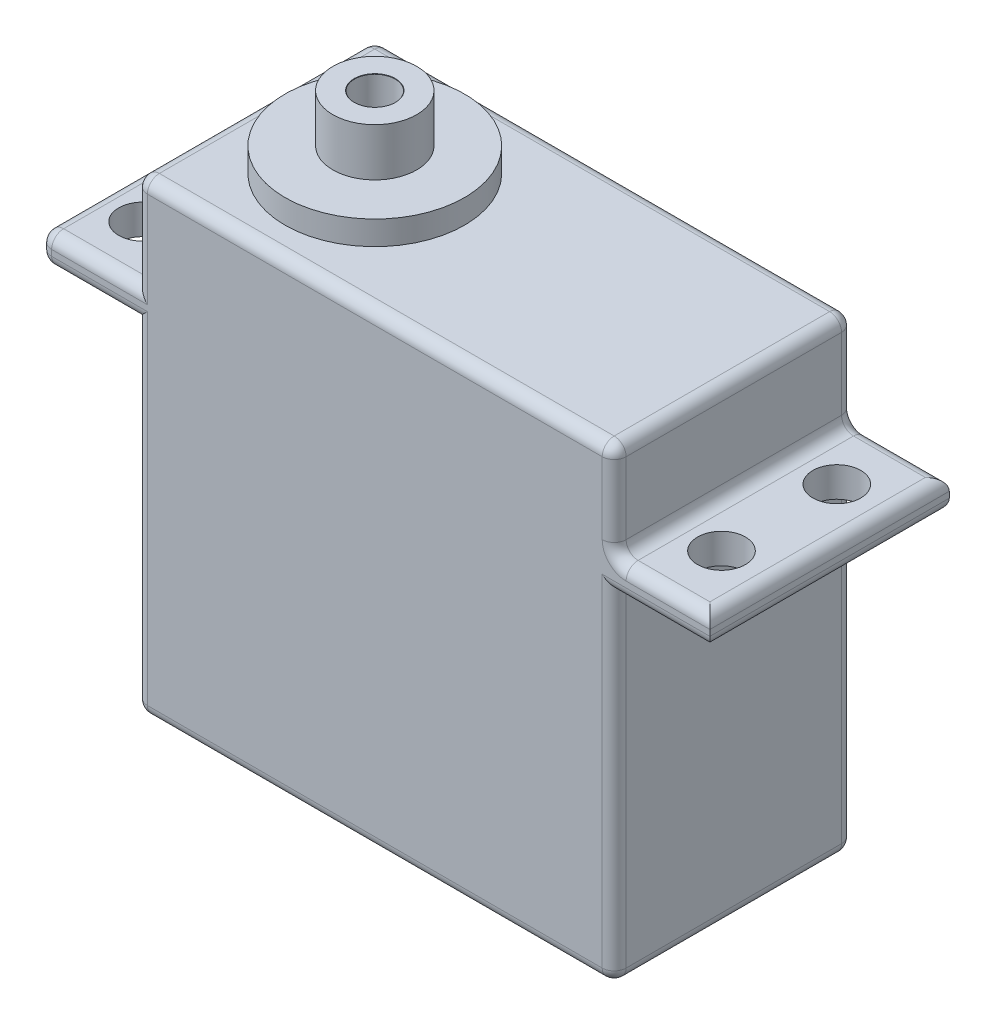
SolidWorks part; units mm, degrees
ref_plane "前视基准面" through (0, 0, 0) normal (0, 0, 1) x (1, 0, 0)
ref_plane "上视基准面" through (0, 0, 0) normal (0, 1, 0) x (1, 0, 0)
ref_plane "右视基准面" through (0, 0, 0) normal (1, 0, 0) x (0, 0, -1)
other "Configuration Table"
sketch "草图1" plane through (0, 0, 0) normal (0, 0, 1) x (1, 0, 0)
  line L1 (-20, -19.5) -> (20, -19.5)
  line L2 (-20, -19.5) -> (-20, 19.5)
  line L3 (-20, 19.5) -> (20, 19.5)
  line L4 (20, -19.5) -> (20, 19.5)
  line L5 (-20, -19.5) -> (20, 19.5) construction
  line L6 (-20, 19.5) -> (20, -19.5) construction
  point P0 (0, 0)
  dimension "D1" = 40
  dimension "D2" = 39
extrude "凸台-拉伸1" add sketch "草图1" against normal blind 20
ref_plane "基准面1" through (20, 0, 0) normal (1, 0, 0) x (0, 0, -1)
ref_plane "基准面2" through (-20, 0, 0) normal (-1, 0, 0) x (0, 0, 1)
sketch "草图2" plane through (20, 0, 0) normal (1, 0, 0) x (0, 0, -1)
  line L0 (0, -19.5) -> (0, 19.5) construction
  line L1 (0, 11.5) -> (20, 11.5)
  line L2 (0, 11.5) -> (0, 9)
  line L3 (0, 9) -> (20, 9)
  line L4 (20, 11.5) -> (20, 9)
  line L5 (20, -19.5) -> (20, 19.5) construction
  line L6 (20, -19.5) -> (0, -19.5) construction
  dimension "D1" = 31
  dimension "D2" = 2.5
extrude "凸台-拉伸2" add sketch "草图2" along normal blind 8
sketch "草图3" plane through (-20, 0, 0) normal (-1, 0, 0) x (0, 0, 1)
  line L0 (-20, 19.5) -> (-20, -19.5) construction
  line L1 (-20, 11.5) -> (0, 11.5)
  line L2 (-20, 11.5) -> (-20, 9)
  line L3 (-20, 9) -> (0, 9)
  line L4 (0, 11.5) -> (0, 9)
  line L5 (0, 19.5) -> (0, -19.5) construction
  line L6 (-20, -19.5) -> (0, -19.5) construction
  dimension "D1" = 31
  dimension "D2" = 2.5
extrude "凸台-拉伸3" add sketch "草图3" along normal blind 8
ref_plane "基准面4" through (0, 11.5, 0) normal (0, 1, 0) x (1, 0, 0)
ref_plane "基准面5" through (0, 11.5, 0) normal (0, 1, 0) x (1, 0, 0)
sketch "草图4" plane through (0, 11.5, 0) normal (0, 1, 0) x (1, 0, 0)
  circle A0 centre (-24.2083, 14.8125) radius 2
  circle A1 centre (-24.2083, 4.8125) radius 2
  circle A2 centre (23.7917, 14.8125) radius 2
  circle A4 centre (23.7917, 5.1765) radius 2
  point P0 (-24.2083, 14.8125)
  point P1 (-24.2083, 4.8125)
  point P2 (23.7917, 14.8125)
  point P3 (23.7917, 5.1765)
  dimension "D3" = 4
  dimension "D4" = 4
  dimension "D5" = 4
  dimension "D6" = 4
  dimension "D1" = 10
  dimension "D2" = 48
extrude "切除-拉伸1" cut sketch "草图4" against normal blind 2.5
ref_plane "基准面7" through (0, 19.5, 0) normal (0, 1, 0) x (1, 0, 0)
sketch "草图6" plane through (0, 19.5, 0) normal (0, 1, 0) x (1, 0, 0)
  line L0 (20, 20) -> (-20, 20) construction
  line L1 (-20, 11) -> (-20, -11) construction
  circle A0 centre (-10, 10) radius 7.5
  dimension "D3" = 15
  dimension "D1" = 10
  dimension "D2" = 10
extrude "凸台-拉伸4" add sketch "草图6" along normal blind 2
sketch "草图8" plane through (0, 19.5, 0) normal (0, 1, 0) x (1, 0, 0)
  line L0 (20, 20) -> (-20, 20) construction
  line L2 (-20, 11) -> (-20, -11) construction
  circle A0 centre (-10, 10) radius 3.5001
  point P6 (-18.3518, -8.0634)
  dimension "D1" = 10
  dimension "D2" = 10
extrude "凸台-拉伸5" add sketch "草图8" along normal blind 6
ref_plane "基准面12" through (0, 25.5, 0) normal (0, 1, 0) x (1, 0, 0)
sketch "草图11" plane through (0, 25.5, 0) normal (0, 1, 0) x (1, 0, 0)
  point P0 (-10, 10)
hole_wizard "M3 间隙孔1" positions "草图12" profile "草图13" hole size "M3" standard "IS"
sketch "草图12" plane through (0, 25.5, 0) normal (0, 1, 0) x (1, 0, 0)
  point P0 (-10, 10)
sketch "草图13" plane through (-10, 25.5, -10) normal (1, 0, 0) x (0, 0, 1)
  line L0 (0, 0) -> (0, 6.0215)
  line L1 (0, 6.0215) -> (1.7, 5)
  line L2 (1.7, 5) -> (1.7, 0.025)
  line L3 (1.7, 0.025) -> (1.725, 0)
  line L5 (1.725, 0) -> (0, 0)
  line L6 (-1.7, 0.025) -> (-1.725, 0) construction
  line L10 (0, 6.0215) -> (-1.7, 5) construction
  line L11 (0, -6.35) -> (0, 107.95) construction
  dimension "孔直径" = 3.4
  dimension "孔深度" = 5
  dimension "近端锥形沉头孔直径" = 3.45
  dimension "近端锥形沉头孔角度" = 90
  dimension "导头角度" = 118
fillet "圆角4" radius 1 30 edges at (24, 11.5, 0) (24, 11.5, -20) (20, 15.5, 0) (20, 19.5, -10) (20, 15.5, -20) (20, 11.5, -10) (-20, 15.5, -20) (28, 11.5, -10) (-28, 11.5, -10) (-28, 10.25, 0) (-28, 10.25, -20) (-24, 9, -20) (-28, 9, -10) (-20, -5.25, -20) (-20, -19.5, -10) (-20, -5.25, 0) (-24, 9, 0) (-24, 11.5, 0) (-20, 15.5, 0) (0, -19.5, -20) (0, -19.5, 0) (20, -19.5, -10) (24, 9, -20) (24, 9, 0) (28, 9, -10) (20, -5.25, -20) (20, -5.25, 0) (0, 19.5, -20) (-20, 19.5, -10) (0, 19.5, 0)
